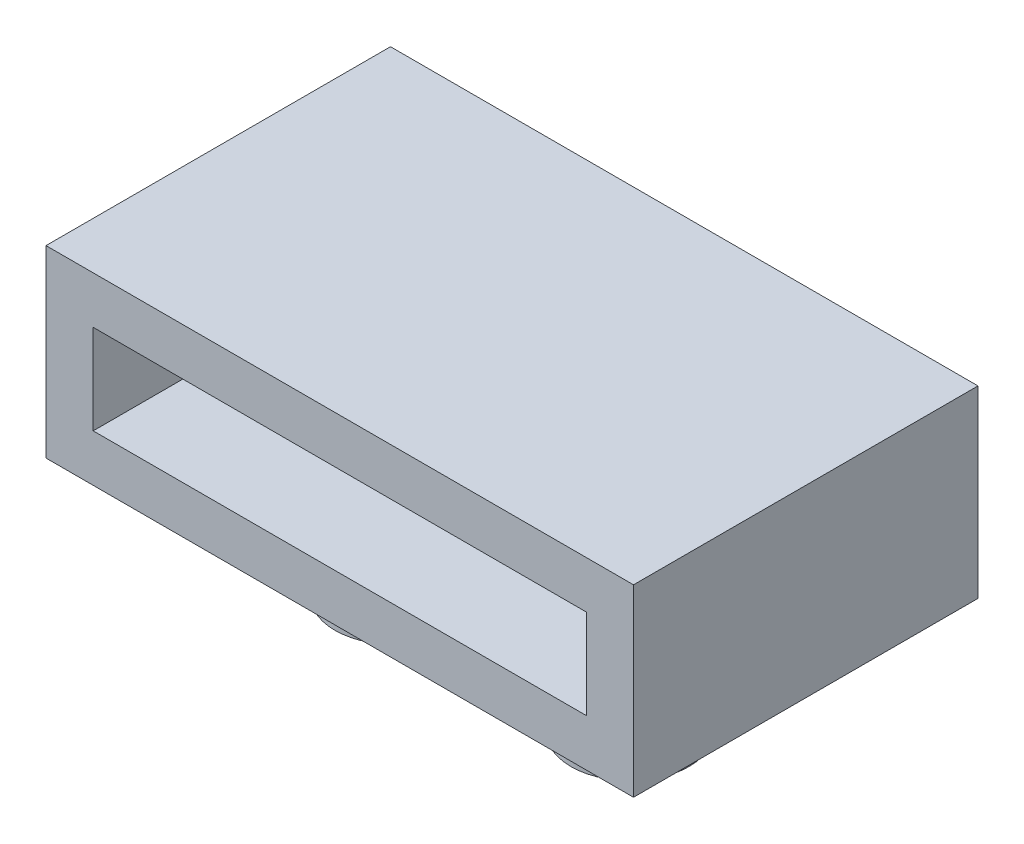
SolidWorks part; units mm, degrees
ref_plane "Front Plane" through (0, 0, 0) normal (0, 0, 1) x (1, 0, 0)
ref_plane "Top Plane" through (0, 0, 0) normal (0, 1, 0) x (1, 0, 0)
ref_plane "Right Plane" through (0, 0, 0) normal (1, 0, 0) x (0, 0, -1)
sketch "Sketch1" plane through (0, 0, 0) normal (0, 1, 0) x (1, 0, 0)
  line L0 (-2, 14.6) -> (22.9, 14.6)
  line L1 (0, 0) -> (20.9, 0)
  line L2 (0, 0) -> (0, 12.6)
  line L3 (0, 12.6) -> (20.9, 12.6)
  line L4 (20.9, 0) -> (20.9, 12.6)
  line L5 (22.9, -2) -> (22.9, 14.6)
  line L6 (-2, -2) -> (22.9, -2)
  line L7 (-2, -2) -> (-2, 14.6)
  line L8 (-2, 0) -> (0, 0)
  line L9 (20.9, 0) -> (22.9, 0)
  dimension "D1" = 12.6
  dimension "D2" = 20.9
  dimension "D3" = 2
extrude "Boss-Extrude1" add sketch "Sketch1" along normal blind 3.8 contours L4 L9 L5 L0 L7 L8 L2 L3 region at (10.45, 0, -14.3114)
extrude "Boss-Extrude2" add sketch "Sketch1<3>" against normal blind 2 contours L1 L4 L3 L2 | L4 L9 L5 L0 L7 L8 L2 L3 region at (10.45, 0, -14.3114) region at (10.45, 0, -6.3)
sketch "Sketch1<3>" plane through (0, 0, 0) normal (0, 1, 0) x (1, 0, 0) same geometry as "Sketch1"
sketch "Sketch3" plane through (0, -2, 0) normal (0, -1, 0) x (1, 0, 0)
  line L0 (10.45, 0) -> (10.45, -14.6) construction
  line L1 (-2, 0) -> (22.9, 0) construction
  line L2 (-2, -14.6) -> (22.9, -14.6) construction
  line L3 (5.45, -7.3) -> (10.45, -7.3) construction
  circle A0 centre (5.45, -7.3) radius 2.5
  circle A1 centre (15.45, -7.3) radius 2.5
  dimension "D1" = 5
  dimension "D2" = 5
extrude "Boss-Extrude4" add sketch "Sketch3" along normal blind 5
sketch "Sketch2" plane through (0, 0, 0) normal (0, 1, 0) x (1, 0, 0)
  line L0 (0, 0) -> (0, 12.6) construction
  line L1 (0, 12.6) -> (20.9, 12.6) construction
  line L2 (20.9, 0) -> (20.9, 12.6) construction
  line L4 (2.6, 11.7) -> (2.6, 8.7) construction
  line L5 (2.6, 8.7) -> (18.3, 8.7) construction
  line L6 (18.3, 8.7) -> (18.3, 11.7) construction
  line L7 (2.1, 11.7) -> (2.1, 8.7)
  line L8 (18.8, 8.7) -> (18.8, 11.7)
  line L9 (3.1, 11.7) -> (3.1, 8.7)
  line L10 (17.8, 8.7) -> (17.8, 11.7)
  circle A0 centre (2.6, 10.2) radius 1.5
  circle A1 centre (18.3, 10.2) radius 1.5
  dimension "D1" = 3
  dimension "D2" = 2.6
  dimension "D3" = 2.4
  dimension "D4" = 2.6
  dimension "D5" = 0.5
  dimension "D6" = 0.5
extrude "Boss-Extrude3" [suppressed] add sketch "Sketch2" along normal blind 2 contours L9 A0 | L7 A0 | L8 A1 | L10 A1
sketch "Sketch4" plane through (0, 3.8, 0) normal (0, 1, 0) x (1, 0, 0)
  line L1 (-2, 14.6) -> (22.9, 14.6)
  line L2 (-2, 14.6) -> (-2, 0)
  line L3 (-2, 0) -> (22.9, 0)
  line L4 (22.9, 14.6) -> (22.9, 0)
extrude "Boss-Extrude5" add sketch "Sketch4" along normal blind 2
